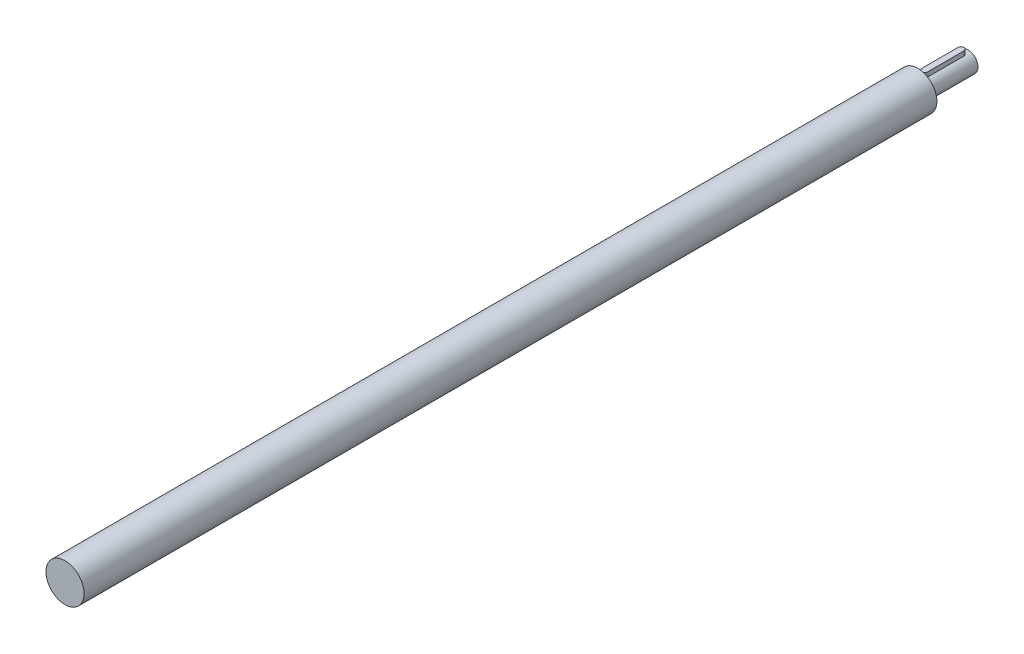
SolidWorks part; units mm, degrees
ref_plane "Płaszczyzna przednia" through (0, 0, 0) normal (0, 0, 1) x (1, 0, 0)
ref_plane "Płaszczyzna górna" through (0, 0, 0) normal (0, 1, 0) x (1, 0, 0)
ref_plane "Płaszczyzna prawa" through (0, 0, 0) normal (1, 0, 0) x (0, 0, -1)
sketch "Szkic1" plane through (0, 0, 0) normal (0, 0, 1) x (1, 0, 0)
  circle A0 centre (0, 0) radius 9.5
extrude "Dodanie-wyciągnięcie1" add sketch "Szkic1" along normal blind 425
sketch "Szkic2" plane through (0, 0, 0) normal (0, 0, -1) x (-1, 0, 0)
  circle A0 centre (0, 0) radius 5
extrude "Dodanie-wyciągnięcie2" add sketch "Szkic2" along normal blind 25
ref_plane "Płaszczyzna2" through (0, 0, -2) normal (0, 0, -1) x (-1, 0, 0)
sketch "Szkic3" plane through (0, 0, -2) normal (0, 0, -1) x (-1, 0, 0)
  line L1 (1.5, 0) -> (-1.5, 0)
  line L2 (1.5, 0) -> (1.5, 7)
  line L3 (1.5, 7) -> (-1.5, 7)
  line L4 (-1.5, 0) -> (-1.5, 7)
  line L5 (1.5, 0) -> (-1.5, 7) construction
  line L6 (1.5, 7) -> (-1.5, 0) construction
  point P0 (0, 0)
  point P7 (0, 3.5)
  dimension "D1" = 7
  dimension "D2" = 3
extrude "Dodanie-wyciągnięcie3" add sketch "Szkic3" along normal blind 21
fillet "Zaokrąglenie2" radius 1.5 1 edges at (-1.5, 5.8848, -23)
fillet "Zaokrąglenie3" radius 1.5 3 edges at (1.5, 5.8848, -2) (-1.5, 5.8848, -2) (1.5, 5.8848, -23)
